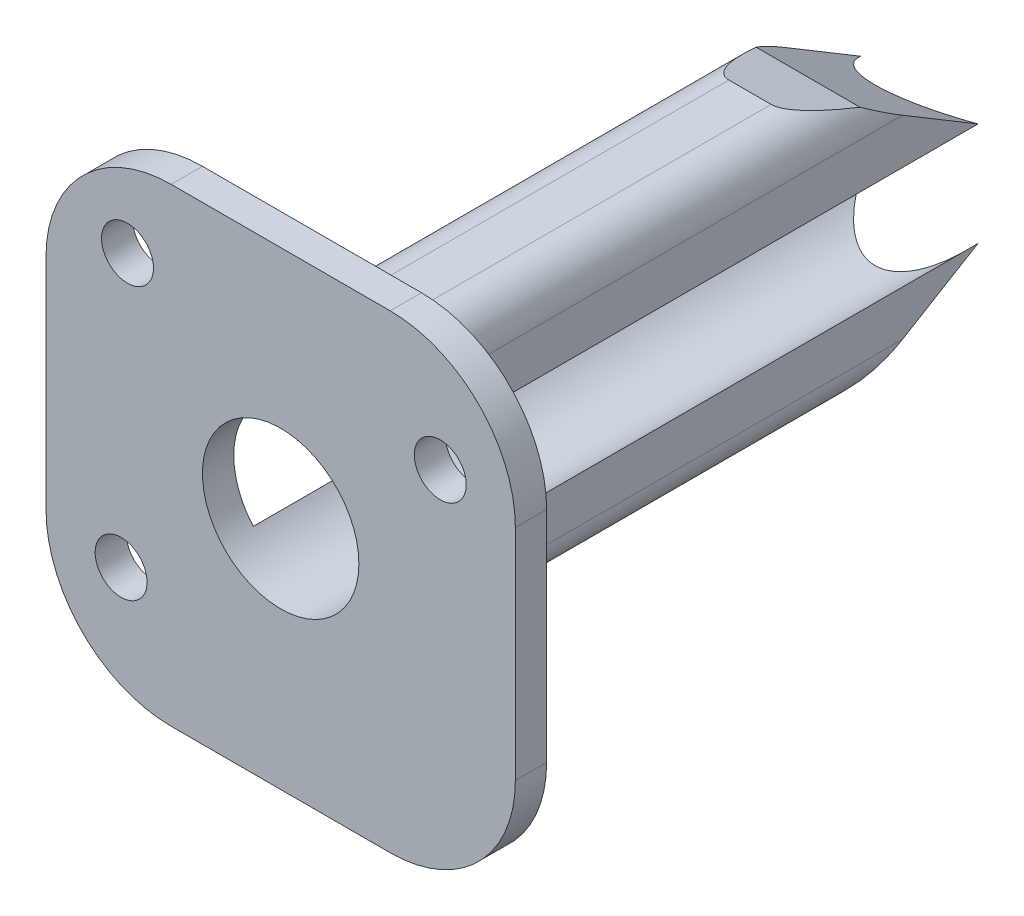
SolidWorks part; units mm, degrees
note: The reader was unsure of these and kept them because the rebuilt part matched: shared geometry of "Croquis2<3>", "Croquis2<4>".
ref_plane "Alzado" through (0, 0, 0) normal (1, 0, 0) x (0, 1, 0)
ref_plane "Planta" through (0, 0, 0) normal (0, 0, 1) x (0, 1, 0)
ref_plane "Vista lateral" through (0, 0, 0) normal (0, 1, 0) x (-1, 0, 0)
sketch "Croquis2" plane through (0, 0, 0) normal (0, 0, 1) x (0, 1, 0)
  line L0 (-21.5, -9.375) -> (21.5, -9.375)
  line L1 (-37.5, -37.5) -> (37.5, -37.5)
  line L2 (-37.5, -37.5) -> (-37.5, 37.5)
  line L3 (-37.5, 37.5) -> (37.5, 37.5)
  line L4 (37.5, -37.5) -> (37.5, 37.5)
  line L5 (-37.5, -37.5) -> (37.5, 37.5) construction
  line L6 (-37.5, 37.5) -> (37.5, -37.5) construction
  line L11 (-21.5, -9.375) -> (-21.5, 9.375)
  line L12 (21.5, -9.375) -> (21.5, 9.375)
  line L13 (-21.5, 9.375) -> (21.5, 9.375)
  line L14 (-21.5, -9.375) -> (21.5, 9.375) construction
  line L15 (21.5, -9.375) -> (-21.5, 9.375) construction
  line L16 (37.5, 0) -> (0, 0) construction
  circle A0 centre (0, 0) radius 12.5
  point P0 (0, 0)
  point P7 (0, 0)
  dimension "D4" = 25
  dimension "D1" = 75
  dimension "D2" = 75
  dimension "D3" = 43
  dimension "D6" = 18.75
extrude "Saliente-Extruir1" add sketch "Croquis2" along normal blind 5 contours A0 L13 L4 L3 L2 L1 L0 L11 | A0 L13 L11 L0 | L0 A0 L13 | L13 A0 | L0 A0 | A0 L0 L4 L13
extrude "Saliente-Extruir2" add sketch "Croquis2<3>" against normal blind 100 contours A0 L13 L11 L0 | A0 L0 L4 L13
sketch "Croquis2<3>" plane through (0, 0, 0) normal (0, 0, 1) x (0, 1, 0) same geometry as "Croquis2"
chamfer "Chaflán1" distance 15 distance2 25 1 edges at (0, 21.5, -100)
chamfer "Chaflán2" distance 25 distance2 15 1 edges at (0, -21.5, -100)
extrude "Cortar-Extruir1" cut sketch "Croquis2<4>" along normal up to next contours L0 A0 L13 | L0 A0 | L13 A0
sketch "Croquis2<4>" plane through (0, 0, 0) normal (0, 0, 1) x (0, 1, 0) same geometry as "Croquis2"
chamfer "Chaflán3" distance 5 2 edges at (0, -21.5, -75) (0, 21.5, -75)
fillet "Redondeo1" radius 6 4 edges at (-9.375, -21.5, -35) (9.375, -21.5, -35) (9.375, 21.5, -35) (-9.375, 21.5, -35)
fillet "Redondeo2" radius 20 4 edges at (-37.5, -37.5, 2.5) (37.5, -37.5, 2.5) (-37.5, 37.5, 2.5) (37.5, 37.5, 2.5)
sketch "Sketch1" plane through (0, 0, 5) normal (0, 0, 1) x (1, 0, 0)
  line L0 (37.5, -17.5) -> (37.5, 17.5) construction
  line L1 (-37.5, -17.5) -> (-37.5, 17.5) construction
  line L2 (17.5, -37.5) -> (-17.5, -37.5) construction
  line L4 (17.5, 37.5) -> (-17.5, 37.5) construction
  circle A0 centre (25.5, 19.5) radius 4.15
  circle A1 centre (-24.48, 24.48) radius 4.15
  circle A2 centre (-25.5, -19.5) radius 4.15
  dimension "D1" = 8.3
  dimension "D2" = 8.3
  dimension "D7" = 8.3
  dimension "D3" = 12
  dimension "D4" = 18
  dimension "D5" = 12
  dimension "D6" = 18
  dimension "D10" = 13.02
  dimension "D11" = 13.02
extrude "Cut-Extrude2" cut sketch "Sketch1" against normal blind 10
